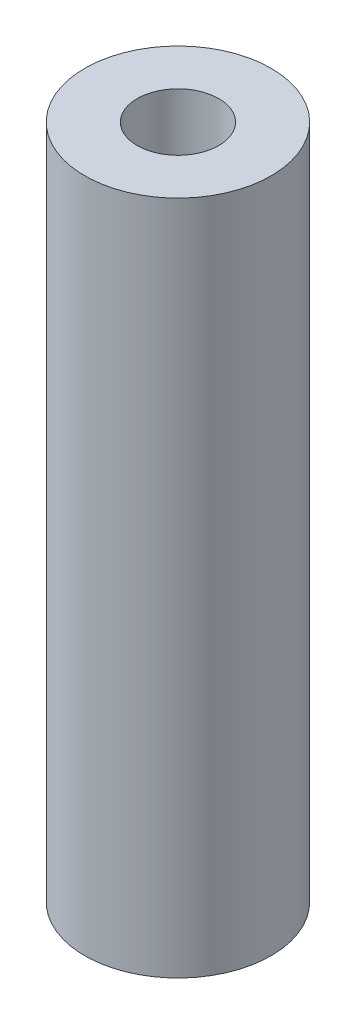
SolidWorks part; units mm, degrees
ref_plane "Front Plane" through (0, 0, 0) normal (0, 0, 1) x (1, 0, 0)
ref_plane "Top Plane" through (0, 0, 0) normal (0, 1, 0) x (1, 0, 0)
ref_plane "Right Plane" through (0, 0, 0) normal (1, 0, 0) x (0, 0, -1)
sketch "Sketch1" plane through (0, 0, 0) normal (0, 1, 0) x (1, 0, 0)
  circle A0 centre (0, 0) radius 4
  circle A1 centre (0, 0) radius 1.75
  dimension "D1" = 8
  dimension "D2" = 3.5
extrude "Boss-Extrude1" add sketch "Sketch1" along normal blind 29
